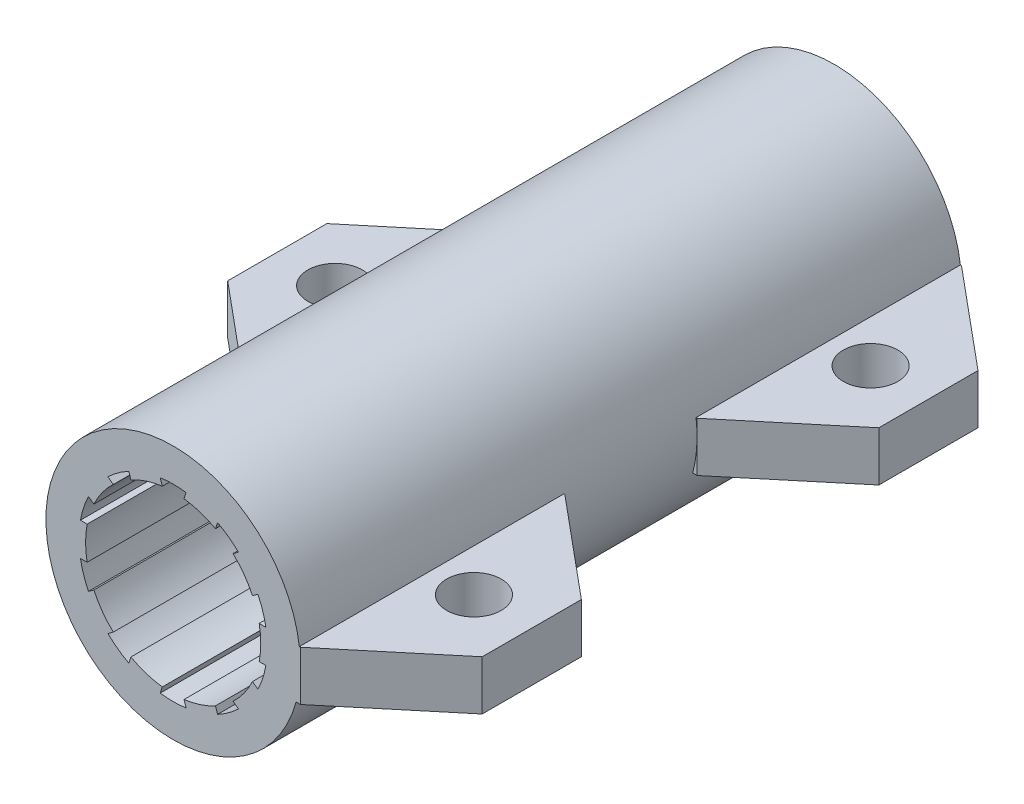
SolidWorks part; units mm, degrees
ref_plane "Plano frontal" through (0, 0, 0) normal (0, 0, 1) x (1, 0, 0)
ref_plane "Plano superior" through (0, 0, 0) normal (0, 1, 0) x (1, 0, 0)
ref_plane "Plano direito" through (0, 0, 0) normal (1, 0, 0) x (0, 0, -1)
sketch "Esboço1" plane through (0, 0, 0) normal (0, 0, 1) x (1, 0, 0)
  circle A0 centre (0, 0) radius 7.7
  circle A1 centre (0, 0) radius 5.7
  dimension "D1" = 11.4
  dimension "D2" = 2
extrude "Ressalto-extrusão1" add sketch "Esboço1" along normal blind 40
sketch "Esboço3" plane through (0, 0, 0) normal (0, 1, 0) x (1, 0, 0)
  line L0 (0, 0) -> (0, -40) construction
  line L1 (7.7, 0) -> (-7.7, 0) construction
  line L2 (-5.7, -40) -> (5.7, -40) construction
  line L3 (7.7, -40) -> (13.7, -35)
  line L4 (7.7, -40) -> (-7.7, -40) construction
  line L5 (7.7, -40) -> (7.7, 0) construction
  line L6 (7.7, 0) -> (-7.7, 0) construction
  line L7 (-7.7, -40) -> (-7.7, 0) construction
  line L8 (13.7, -35) -> (13.7, -29)
  line L9 (13.7, -29) -> (7.7, -24)
  line L10 (7.7, -24) -> (6.7, -24)
  line L11 (6.7, -24) -> (6.7, -40)
  line L12 (6.7, -40) -> (7.7, -40)
  line L13 (7.7, 0) -> (13.7, -5)
  line L14 (13.7, -5) -> (13.7, -11)
  line L15 (13.7, -11) -> (7.7, -16)
  line L16 (7.7, -16) -> (6.7, -16)
  line L17 (6.7, -16) -> (6.7, 0)
  line L18 (6.7, 0) -> (7.7, 0)
  line L19 (-7.7, -28) -> (-13.7, -23)
  line L20 (-13.7, -23) -> (-13.7, -17)
  line L21 (-13.7, -17) -> (-7.7, -12)
  line L22 (-7.7, -12) -> (-6.7, -12)
  line L23 (-6.7, -12) -> (-6.7, -28)
  line L24 (-6.7, -28) -> (-7.7, -28)
  line L25 (13.7, -32) -> (6.7, -32) construction
  line L26 (13.7, -8) -> (6.7, -8) construction
  line L27 (-6.7, -20) -> (-13.7, -20) construction
  point P35 (0, -20)
  dimension "D1" = 16
  dimension "D2" = 6
  dimension "D3" = 1
  dimension "D4" = 6
extrude "Ressalto-extrusão3" add sketch "Esboço3" along normal blind 1 and the other way blind 2
sketch "Esboço4" plane through (0, 1, 0) normal (0, 1, 0) x (1, 0, 0)
  line L0 (13.7, -35) -> (13.7, -29) construction
  line L1 (-13.7, -17) -> (-13.7, -23) construction
  line L2 (13.7, -11) -> (13.7, -5) construction
  circle A0 centre (10.2, -32) radius 1.65
  circle A1 centre (10.2, -8) radius 1.65
  circle A2 centre (-10.2, -20) radius 1.65
  point P9 (13.7, -32)
  point P13 (-13.7, -20)
  point P16 (13.7, -8)
  dimension "D2" = 3.3
  dimension "D1" = 3.5
  dimension "D3" = 3.5
  dimension "D4" = 3.5
extrude "Corte-extrusão1" cut sketch "Esboço4" against normal through all
sketch "Esboço5" plane through (0, 0, 40) normal (0, 0, 1) x (1, 0, 0)
  line L0 (0, 0) -> (-13.7805, 0) construction
  line L2 (-3, 1) -> (-6.8902, 1)
  line L3 (-3, 1) -> (-3, -1)
  line L4 (-3, -1) -> (-6.8902, -1)
  line L5 (-6.8902, 1) -> (-6.8902, -1)
  line L6 (-3, 1) -> (-6.8902, -1) construction
  line L7 (-3, -1) -> (-6.8902, 1) construction
  point P3 (-4.9451, 0)
  point P10 (-6.8902, 0)
  dimension "D1" = 3
  dimension "D2" = 2
extrude "Ressalto-extrusão4" add sketch "Esboço5" against normal up to surface (40 mm away) up to face at (3.813, -0.2475, 0)
ref_axis "Eixo1" through (0, 0, 40) along (0, 0, -1)
pattern_circular "PadrãoCircular1" count 10 over 360 about axis through (0, 0, 40) along (0, 0, -1) of "Ressalto-extrusão4"
sketch "Esboço6" plane through (0, 0, 40) normal (0, 0, 1) x (1, 0, 0)
  circle A0 centre (0, 0) radius 5.3
  dimension "D1" = 10.6
extrude "Corte-extrusão2" cut sketch "Esboço6" against normal through all
